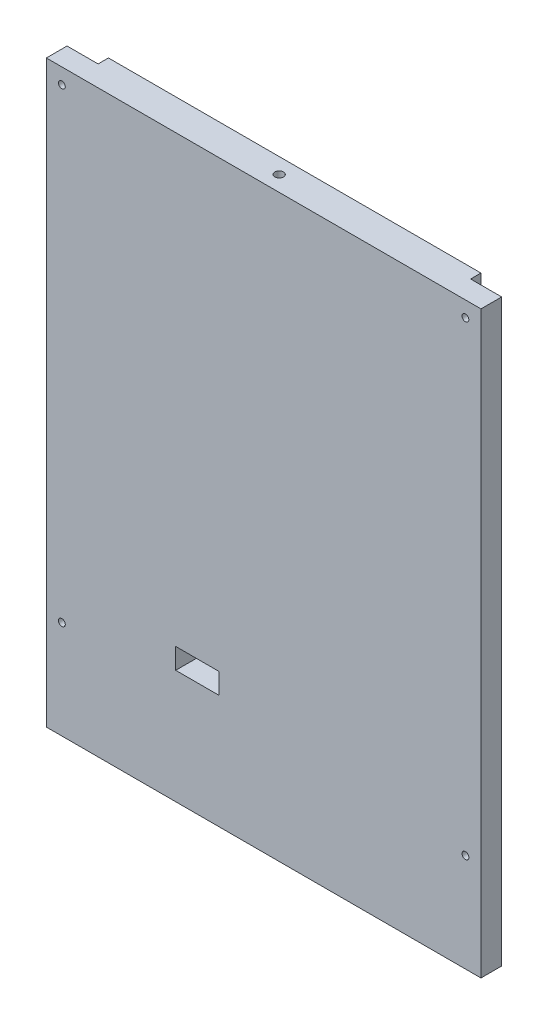
SolidWorks part; units mm, degrees
ref_plane "Front Plane" through (0, 0, 0) normal (0, 0, 1) x (1, 0, 0)
ref_plane "Top Plane" through (0, 0, 0) normal (0, 1, 0) x (1, 0, 0)
ref_plane "Right Plane" through (0, 0, 0) normal (1, 0, 0) x (0, 0, -1)
sketch "Sketch3" plane through (0, 0, 0) normal (0, 1, 0) x (1, 0, 0)
  line L0 (-105, 0) -> (105, 0)
  line L1 (105, 0) -> (105, -10)
  line L2 (105, -10) -> (-105, -10)
  line L3 (-105, -10) -> (-105, 0)
  dimension "D1" = 210
  dimension "D2" = 10
extrude "Boss-Extrude1" add sketch "Sketch3" along normal blind 240
ref_plane "Plane1" through (0, 35, 0) normal (0, 1, 0) x (1, 0, 0)
sketch "Sketch5" plane through (0, 240, 0) normal (0, 1, 0) x (1, 0, 0)
  line L0 (-90, 0) -> (-90, 5)
  line L1 (105, 0) -> (-105, 0) construction
  line L2 (-90, 5) -> (90, 5)
  line L3 (90, 5) -> (90, 0)
  line L4 (-105, 0) -> (-105, -10) construction
  line L5 (105, 0) -> (90, 0)
  line L9 (-105, 0) -> (-105, -10)
  line L10 (-105, -10) -> (105, -10)
  line L11 (105, -10) -> (105, 0)
  line L12 (105, 0) -> (-105, 0)
  line L13 (-105, 0) -> (-105, -10)
  line L14 (-105, -10) -> (105, -10)
  line L15 (105, -10) -> (105, 0)
  line L16 (-90, 0) -> (-105, 0)
  dimension "D1" = 180
  dimension "D2" = 5
  dimension "D3" = 15
  dimension "D4" = 0
extrude "Boss-Extrude2" add sketch "Sketch5" against normal up to surface (205 mm away) up to plane "Plane1"
sketch "Sketch6" plane through (0, 35, 0) normal (0, 1, 0) x (1, 0, 0)
  line L0 (-22.5, 0) -> (-22.5, 15)
  line L2 (-22.5, 15) -> (22.5, 15)
  line L3 (22.5, 15) -> (22.5, 0)
  line L4 (22.5, 0) -> (-22.5, 0)
  line L6 (90, 5) -> (-90, 5) construction
  dimension "D1" = 45
  dimension "D2" = 10
extrude "Boss-Extrude3" add sketch "Sketch6" against normal blind 10
sketch "Sketch7" plane through (0, 0, 10) normal (0, 0, 1) x (1, 0, 0)
  line L0 (0, -1000) -> (0, 49000) construction
  line L1 (-105, 240) -> (105, 240) construction
  line L2 (-105, 240) -> (-105, 0) construction
  line L3 (8.25, 0) -> (-8.25, 0) construction
  circle A0 centre (-97.5, 232.5) radius 1.65
  circle A1 centre (-97.5, 7.5) radius 1.65
  circle A2 centre (97.5, 7.5) radius 1.65
  circle A3 centre (97.5, 232.5) radius 1.65
  dimension "D1" = 3.3
  dimension "D2" = 7.5
  dimension "D4" = 7.5
  dimension "D3" = 7.5
  dimension "D5" = 7.5
extrude "Cut-Extrude1" cut sketch "Sketch7" against normal up to surface (10 mm away) up to face at (0, 95.8333, 0)
sketch "Sketch8" plane through (0, 0, 10) normal (0, 0, 1) x (1, 0, 0)
  line L0 (-105, 240) -> (-105, 0) construction
  line L1 (-42.5, 25) -> (-21.5, 25)
  line L2 (-42.5, 25) -> (-42.5, 15)
  line L3 (-42.5, 15) -> (-21.5, 15)
  line L4 (-21.5, 25) -> (-21.5, 15)
  line L5 (-105, 0) -> (105, 0) construction
  line L6 (0, -1000) -> (0, 49000) construction
  line L7 (42.5, 15) -> (21.5, 15)
  line L8 (21.5, 25) -> (21.5, 15)
  line L9 (42.5, 25) -> (21.5, 25)
  line L10 (42.5, 25) -> (42.5, 15)
  dimension "D1" = 62.5
  dimension "D2" = 15
  dimension "D3" = 21
  dimension "D4" = 10
extrude "Cut-Extrude2" cut sketch "Sketch8" against normal up to surface (10 mm away) contours L4 L1 L2 L3 region at (-32, 20, 10) up to face at (99.15, 232.5, 0)
sketch "Sketch9" plane through (0, 0, 0) normal (0, -1, 0) x (1, 0, 0)
  line L4 (-105, 10) -> (-105, 0)
  line L5 (-105, 0) -> (105, 0)
  line L6 (105, 0) -> (105, 10)
  line L7 (105, 10) -> (-105, 10)
  line L8 (-105, 10) -> (-105, 0)
  line L9 (-105, 0) -> (105, 0)
  line L10 (105, 0) -> (105, 10)
  line L11 (105, 10) -> (-105, 10)
  dimension "D1" = 0
extrude "Boss-Extrude4" add sketch "Sketch9" along normal blind 40
sketch "Sketch10" plane through (0, 240, 0) normal (0, 1, 0) x (1, 0, 0)
  line L0 (-105, -10) -> (105, -10) construction
  circle A0 centre (0, -2.5) radius 2.1
  dimension "D1" = 4.2
  dimension "D2" = 7.5
extrude "Cut-Extrude3" cut sketch "Sketch10" against normal blind 4.5
